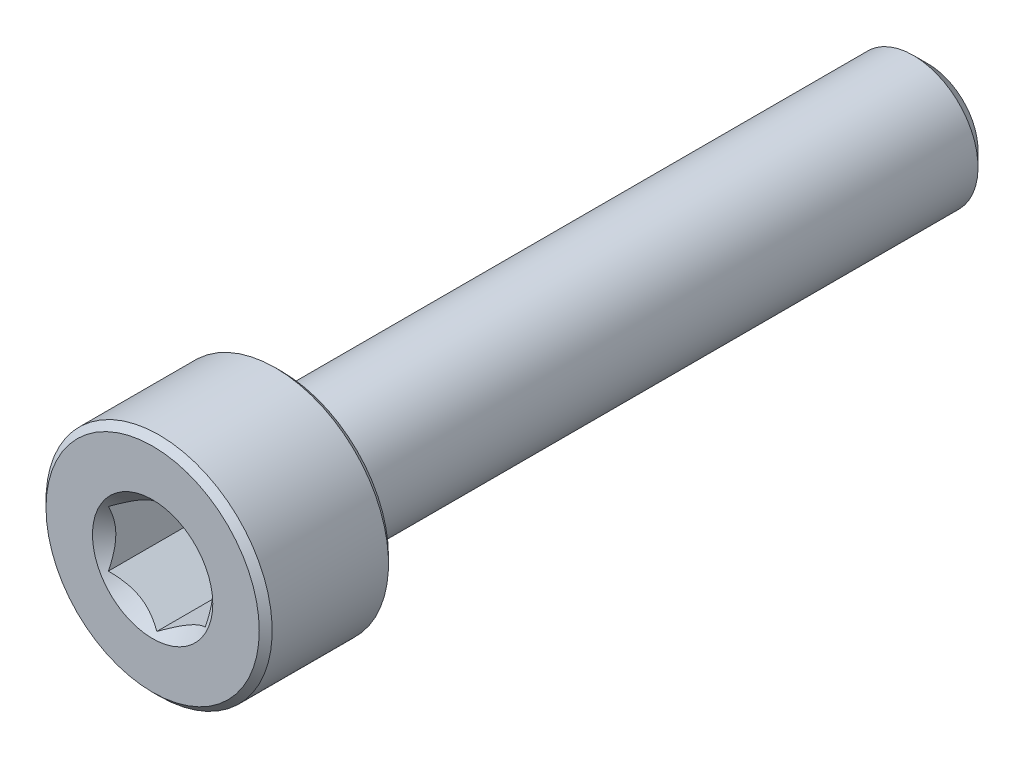
SolidWorks part; units mm, degrees
ref_plane "Front Plane" through (0, 0, 0) normal (0, 0, 1) x (1, 0, 0)
ref_plane "Top Plane" through (0, 0, 0) normal (0, 1, 0) x (1, 0, 0)
ref_plane "Right Plane" through (0, 0, 0) normal (1, 0, 0) x (0, 0, -1)
sketch "Sketch1" plane through (0, 0, 0) normal (1, 0, 0) x (0, 0, -1)
  line L0 (-12, 0) -> (12, 0) construction
  line L1 (12, 0) -> (12, 1.5453) construction
  line L2 (12, 1.5453) -> (11.5453, 2) construction
  line L3 (11.5453, 2) -> (11.475, 2) construction
  line L4 (11.475, 2) -> (-8, 2) construction
  line L5 (-8, 2) -> (-8, 3.5) construction
  line L6 (-8, 3.5) -> (-12, 3.5) construction
  line L7 (-12, 3.5) -> (-12, 0) construction
  line L8 (12, 1.5453) -> (12, 2) construction
  line L9 (11.9563, 2.0758) -> (12.3063, 1.4696) construction
  line L10 (12.3063, 1.4696) -> (12.6563, 2.0758) construction
  line L11 (12.6563, 2.0758) -> (11.9563, 2.0758) construction
  line L12 (12.3063, 2.0758) -> (12.3063, 2) construction
  line L13 (12.3063, 1.4696) -> (12.3063, 1.5453) construction
  line L14 (12.2625, 1.5453) -> (12.35, 1.5453) construction
  line L15 (12, 2) -> (12.6125, 2) construction
  line L16 (11.9781, 2.0379) -> (12.6344, 2.0379) construction
  line L17 (12, 0) -> (12, -2) construction
  line L18 (-8.2, 3.5) -> (-8, 3.3) construction
  line L19 (-11.8, 3.5) -> (-12, 3.3) construction
  line L20 (-8, 2) -> (-8, 0) construction
  line L21 (-8, 1) -> (-1.3333, 1) construction
  line L22 (-1.3333, 1) -> (5.3333, 1) construction
  line L23 (5.3333, 1) -> (12, 1) construction
  line L24 (-1.3333, 1) -> (-1.3333, 2) construction
  line L25 (-1.3333, 2) -> (-1.3333, 3.5) construction
  line L26 (5.3333, 1) -> (5.3333, 3.5) construction
  point P0 (-12, 1.5)
  point P3 (10.25, 2)
  point P4 (0, 0)
  point P18 (5.3333, 2)
  point P22 (12.3063, 1.5453)
  point P24 (11.475, 2)
  point P25 (12.3063, 2)
  point P28 (12.3063, 2.0379)
  point P29 (10.25, -2)
  point P30 (-1.3333, 2)
  point P31 (-10, 3.5)
  point P37 (-8.7, 3.5)
  point P38 (-11.7, 3.5)
  point P45 (-1.3333, 1)
  point P46 (5.3333, 1)
  dimension "D2" = 0.0875
  dimension "D7" = 0.2
  dimension "D8" = 0.2
  dimension "D9" = 0.2
  dimension "D10" = 0.1
  dimension "D11" = 0.5
  dimension "Drive Size" = 3
  dimension "Head Diameter" = 7
  dimension "Head Height" = 4
  dimension "Thread Pitch" = 0.7
  dimension "Thread Dia" = 4
  dimension "Length" = 20
  dimension "D12" = 0.525
  dimension "D4" = 1.75
  dimension "D3" = 45
sketch "Sketch2" plane through (0, 0, 0) normal (1, 0, 0) x (0, 0, -1)
  line L0 (-12, 0) -> (-12, 3.3)
  line L1 (-11.8, 3.5) -> (-8.2, 3.5)
  line L2 (-8, 3.3) -> (-8, 2.2)
  line L4 (11.5453, 2) -> (12, 1.5453)
  line L5 (12, 1.5453) -> (12, 0)
  line L6 (-8, 3.5) -> (-12, 3.5) construction
  line L7 (12, 0) -> (-12, 0)
  line L8 (-11.8, 3.5) -> (-12, 3.3) construction
  line L10 (-11.8, 3.5) -> (-12, 3.3)
  line L14 (-8.2, 3.5) -> (-8, 3.3) construction
  line L16 (-8.2, 3.5) -> (-8, 3.3)
  line L17 (-8, 2) -> (-8, 3.5) construction
  line L19 (-7.8, 2) -> (11.5453, 2)
  line L20 (11.475, 2) -> (-8, 2) construction
  arc A1 (-8, 2.2) -> (-7.8, 2) centre (-7.8, 2.2) ccw
  dimension "D3" = 0.2
revolve "Revolve1" add sketch "Sketch2" angle 360 about L7
sketch "Sketch3" plane through (0, 0, 12) normal (0, 0, 1) x (1, 0, 0)
  line L1 (1.5, -0.866) -> (1.5, 0.866)
  line L2 (1.5, 0.866) -> (0, 1.7321)
  line L3 (0, 1.7321) -> (-1.5, 0.866)
  line L4 (-1.5, 0.866) -> (-1.5, -0.866)
  line L5 (-1.5, -0.866) -> (0, -1.7321)
  line L6 (0, -1.7321) -> (1.5, -0.866)
  circle A0 centre (0, 0) radius 1.5 construction
  circle A1 centre (0, 0) radius 3.5 construction
  circle A2 centre (0, 0) radius 3.5 construction
  circle A3 centre (0, 0) radius 1.7321 construction
  point P13 (0, 0)
  dimension "D1" = 3.4641
extrude "Cut-Extrude1" cut sketch "Sketch3" against normal offset from surface (3 mm away) 1 up to face at (0, 3.3, 8)
sketch "Sketch4" plane through (0, 0, 12) normal (0, 0, 1) x (1, 0, 0)
  circle A0 centre (0, 0) radius 1.862
  dimension "D1" = 3.7239
extrude "Cut-Extrude2" cut sketch "Sketch4" against normal up to vertex (2 mm away) draft 45 up to point (0, 3.5, 10)
sketch "Sketch11" plane through (0, 0, 0) normal (1, 0, 0) x (0, 0, -1)
  line L0 (-12, 0) -> (12, 0) construction
  line L1 (-12, 0) -> (12, 0) construction
  line L2 (-4.25, 0) -> (-4.25, 2) construction
  line L3 (11.475, 2) -> (-8, 2) construction
  line L4 (8.25, 0) -> (8.25, 2) construction
  line L6 (12, 1.5453) -> (12, 2) construction
  point P2 (-4.25, 0)
  point P3 (8.25, 0)
  dimension "D1" = 3.75
  dimension "D2" = 3.75
sketch "Sketch6" [suppressed] plane through (0, 0, -12) normal (0, 0, -1) x (-1, 0, 0)
  circle A0 centre (0, 0) radius 2
curve "Helix/Spiral1" [suppressed] pitch 0.7 height 20.7 turns 29.5714
sketch "Sketch10" [suppressed] plane through (0, 0, 0) normal (1, 0, 0) x (0, 0, -1)
  line L0 (-7.8, -3.5) -> (-7.8, 3.5)
  line L5 (-12, 0) -> (12, 0) construction
  line L6 (-7.8, 2) -> (-7.8, -2) construction
  point P3 (-7.8, 0)
split "Split1" [suppressed] bodies to split 106
sketch "Sketch7" [suppressed] plane through (0, 0, 0) normal (1, 0, 0) x (0, 0, -1)
  line L0 (11.9781, 2.0379) -> (12.6344, 2.0379)
  line L1 (12.6344, 2.0379) -> (12.35, 1.5453)
  line L2 (12.35, 1.5453) -> (12.2625, 1.5453)
  line L3 (12.2625, 1.5453) -> (11.9781, 2.0379)
sweep "Cut-Sweep1" [suppressed] cut profiles "Sketch7" path "Helix/Spiral1"
sketch "Sketch8" [suppressed] plane through (0, 0, 0) normal (1, 0, 0) x (0, 0, -1)
  line L0 (-8, 0) -> (-8, 2)
  line L1 (-7.8, -2) -> (-7.8, 2) construction
  line L2 (-8, 2) -> (-7.8, 2)
  line L4 (-7.8, 2) -> (-6.6453, 0)
  line L5 (-6.6453, 0) -> (-8, 0)
  line L6 (11.475, 2) -> (-8, 2) construction
  line L7 (-12, 0) -> (12, 0) construction
  dimension "D1" = 60
revolve "Revolve2" [suppressed] add sketch "Sketch8" angle 360 about L5
equation "\"D2@Sketch1\" = \"Thread Pitch@Sketch1\" / 8"
equation "\"D4@Helix/Spiral1\" = \"Thread Pitch@Sketch1\""
equation "\"D7@Sketch1\" = \"Head Height@Sketch1\" * .05"
equation "\"D8@Sketch1\"=\"D7@Sketch1\""
equation "\"D9@Sketch1\"=\"D7@Sketch1\""
equation "\"D10@Sketch1\"=\"D7@Sketch1\"/2"
equation "\"D11@Sketch1\"=\"D10@Sketch1\"*5"
equation "\"D4@Sketch1\"=\"Thread Pitch@Sketch1\"*2.5"
equation "\"D12@Sketch1\"=\"Thread Pitch@Sketch1\"*.75"
equation "\"D3@Helix/Spiral1\"=\"Length@Sketch1\"+\"Thread Pitch@Sketch1\""
equation "\"D3@Sketch2\"=\"Thread Dia@Sketch1\"*0.05"
equation "\"D1@Sketch11\"=\"Length@Sketch1\"*0.1875"
equation "\"D2@Sketch11\"=\"D1@Sketch11\""
equation "\"D1@Sketch4\"=\"D1@Sketch3\"*1.075"
